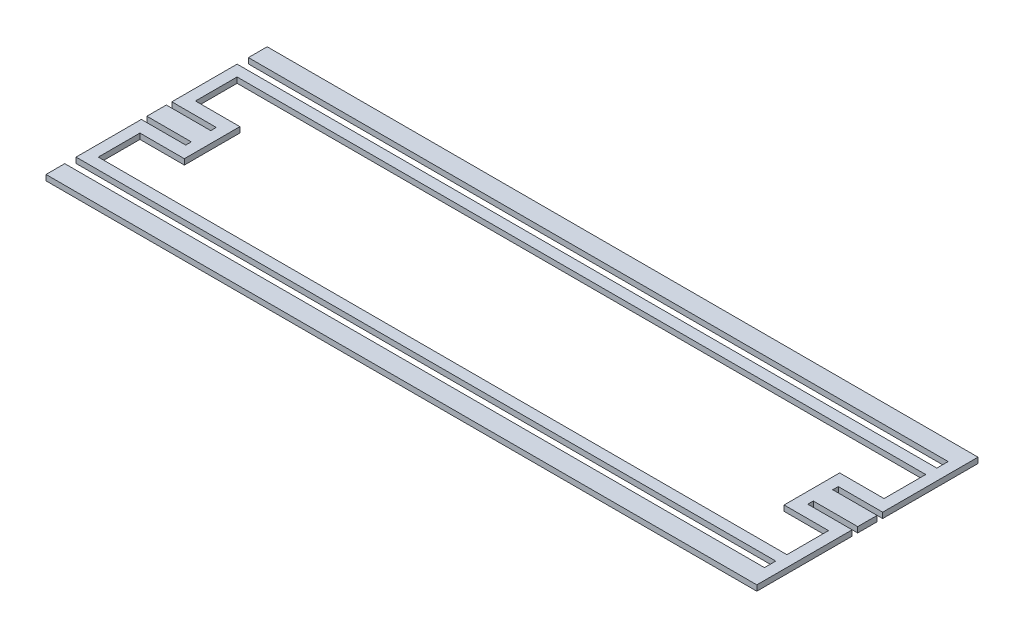
SolidWorks part; units mm, degrees
ref_plane "Front Plane" through (0, 0, 0) normal (0, 0, 1) x (1, 0, 0)
ref_plane "Top Plane" through (0, 0, 0) normal (0, 1, 0) x (1, 0, 0)
ref_plane "Right Plane" through (0, 0, 0) normal (1, 0, 0) x (0, 0, -1)
sketch "Sketch1" plane through (0, 0, 0) normal (0, 1, 0) x (1, 0, 0)
  line L0 (-203.2, 46.0343) -> (-203.2, 8.7313)
  line L1 (-203.2, 63.2269) -> (203.2, 63.2269)
  line L2 (-203.2, 63.2269) -> (-203.2, 52.5113)
  line L3 (-203.2, -63.2269) -> (203.2, -63.2269)
  line L4 (203.2, 63.2269) -> (203.2, 8.7313)
  line L5 (-203.2, 63.2269) -> (203.2, -63.2269) construction
  line L6 (-203.2, -63.2269) -> (203.2, 63.2269) construction
  line L7 (-203.2, -63.2269) -> (190.5, -63.2269)
  line L8 (-203.2, -63.2269) -> (-203.2, -52.5113)
  line L9 (-203.2, -52.5113) -> (196.85, -52.5113)
  line L11 (-203.2, 63.2269) -> (190.5, 63.2269)
  line L12 (-203.2, 63.2269) -> (-203.2, 52.5113)
  line L13 (-203.2, 52.5113) -> (196.85, 52.5113)
  line L15 (-203.2, -52.5113) -> (196.85, -52.5113)
  line L17 (-203.2, -46.0343) -> (196.85, -46.0343)
  line L18 (196.85, -52.5113) -> (196.85, -46.0343)
  line L19 (-203.2, 52.5113) -> (196.85, 52.5113)
  line L21 (-203.2, 46.0343) -> (196.85, 46.0343)
  line L22 (196.85, 52.5113) -> (196.85, 46.0343)
  line L23 (-203.2, -52.5113) -> (-203.2, -63.2269)
  line L24 (196.85, 15.875) -> (171.45, 15.875)
  line L25 (-196.85, -39.6843) -> (196.85, -39.6843)
  line L26 (-196.85, -39.6843) -> (-196.85, -15.875)
  line L27 (-196.85, 39.6843) -> (196.85, 39.6843)
  line L28 (196.85, -39.6843) -> (196.85, -15.875)
  line L29 (-196.85, -39.6843) -> (196.85, 39.6843) construction
  line L30 (-196.85, 39.6843) -> (196.85, -39.6843) construction
  line L31 (171.45, 15.875) -> (171.45, -15.875)
  line L32 (171.45, -15.875) -> (196.85, -15.875)
  line L33 (196.85, 8.7313) -> (177.8, 8.7313)
  line L34 (177.8, 8.7313) -> (177.8, 5.5563)
  line L35 (177.8, 5.5563) -> (196.85, 5.5563)
  line L36 (196.85, -5.5562) -> (177.8, -5.5563)
  line L37 (177.8, -5.5563) -> (177.8, -8.7312)
  line L38 (177.8, -8.7312) -> (196.85, -8.7312)
  line L39 (177.8, 5.5563) -> (177.8, -5.5563) construction
  line L40 (196.85, 8.7313) -> (203.2, 8.7313)
  line L41 (196.85, 5.5563) -> (203.2, 5.5563)
  line L42 (196.85, -8.7312) -> (203.2, -8.7312)
  line L43 (196.85, -5.5562) -> (203.2, -5.5562)
  line L44 (196.85, -5.5562) -> (196.85, 5.5563) construction
  line L45 (196.85, 5.5563) -> (196.85, 8.7313) construction
  line L46 (196.85, 8.7313) -> (196.85, 15.875) construction
  line L47 (196.85, 15.875) -> (196.85, 39.6843)
  line L48 (196.85, -15.875) -> (196.85, -8.7312) construction
  line L49 (196.85, -8.7312) -> (196.85, -5.5562) construction
  line L50 (203.2, -5.5562) -> (203.2, -8.7312) construction
  line L51 (203.2, -8.7312) -> (203.2, -63.2269)
  line L52 (203.2, 8.7313) -> (203.2, 5.5563) construction
  line L53 (203.2, 5.5563) -> (203.2, -5.5562)
  line L54 (0, 39.6843) -> (0, -39.6843) construction
  line L55 (-196.85, 8.7313) -> (-203.2, 8.7313)
  line L56 (-196.85, 5.5563) -> (-203.2, 5.5563)
  line L57 (-196.85, -5.5562) -> (-203.2, -5.5562)
  line L58 (-196.85, -8.7312) -> (-203.2, -8.7312)
  line L59 (-171.45, -15.875) -> (-196.85, -15.875)
  line L60 (-177.8, 8.7313) -> (-177.8, 5.5563)
  line L61 (-177.8, -5.5563) -> (-177.8, -8.7312)
  line L62 (-177.8, -8.7312) -> (-196.85, -8.7312)
  line L63 (-196.85, -5.5562) -> (-177.8, -5.5563)
  line L64 (-177.8, 5.5563) -> (-196.85, 5.5563)
  line L65 (-196.85, 8.7313) -> (-177.8, 8.7313)
  line L66 (-171.45, 15.875) -> (-171.45, -15.875)
  line L67 (-196.85, 15.875) -> (-171.45, 15.875)
  line L68 (-203.2, 5.5563) -> (-203.2, -5.5562)
  line L69 (-196.85, 15.875) -> (-196.85, 39.6843)
  line L71 (-203.2, -8.7312) -> (-203.2, -46.0343)
  point P0 (0, 0)
  point P16 (0, 0)
  point P26 (171.45, 0)
  point P35 (177.8, 0)
  point P36 (-171.45, 0)
  point P43 (0, 39.6843)
  dimension "D1" = 406.4
  dimension "D2" = 126.4539
  dimension "D4" = 10.7156
  dimension "D5" = 10.7156
  dimension "D6" = 6.477
  dimension "D7" = 6.477
  dimension "D3" = 6.35
  dimension "D8" = 6.35
  dimension "D9" = 6.35
  dimension "D10" = 6.35
  dimension "D11" = 25.4
  dimension "D12" = 31.75
  dimension "D13" = 3.175
  dimension "D14" = 3.175
  dimension "D15" = 17.4625
  dimension "D16" = 19.05
extrude "Boss-Extrude1" add sketch "Sketch1" along normal mid plane 3.175 contours L1 L13 L2 L9 L3 L4 region at (-3.175, 0, -41.7781)
equation "\"D2@Sketch1\"        = 5.698in - ( 2 * ( 2 * 0.125in))- 4*3/64-(0.008*4)"
equation "\"D1@Sketch1\"=16.00in"
equation "\"D6@Sketch1\"=\"D7@Sketch1\""
